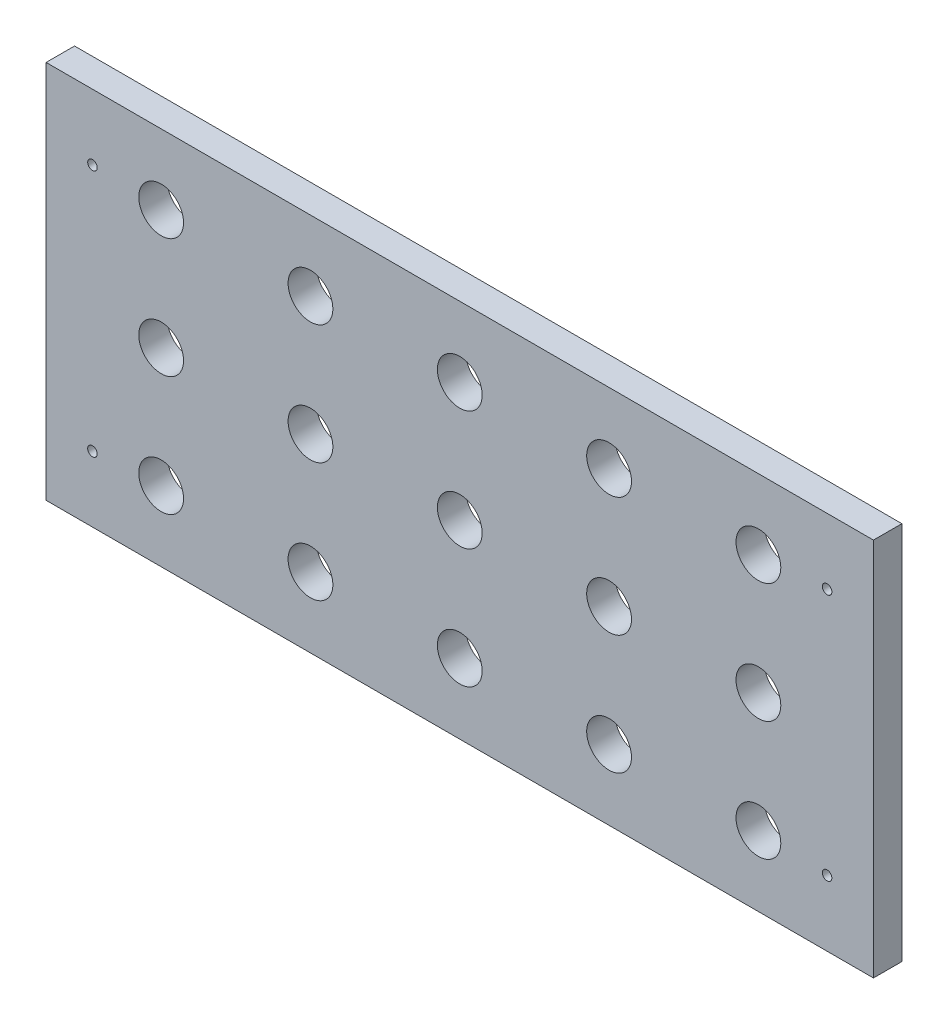
SolidWorks part; units mm, degrees
ref_plane "Front Plane" through (0, 0, 0) normal (0, 0, 1) x (1, 0, 0)
ref_plane "Top Plane" through (0, 0, 0) normal (0, 1, 0) x (1, 0, 0)
ref_plane "Right Plane" through (0, 0, 0) normal (1, 0, 0) x (0, 0, -1)
sketch "Sketch1" plane through (0, 0, 0) normal (0, 0, 1) x (1, 0, 0)
  line L1 (0, 0) -> (277.05, 0)
  line L2 (0, 0) -> (0, 127)
  line L3 (0, 127) -> (277.05, 127)
  line L4 (277.05, 0) -> (277.05, 127)
  line L5 (9.525, 127) -> (9.525, 0) construction
  line L7 (267.525, 127) -> (267.525, 0) construction
  circle A3 centre (15.525, 105) radius 1.6
  circle A4 centre (15.525, 22) radius 1.6
  circle A5 centre (261.525, 105) radius 1.6
  circle A6 centre (261.525, 22) radius 1.6
  dimension "D14" = 3.2
  dimension "D17" = 3.2
  dimension "D19" = 3.2
  dimension "D20" = 3.2
  dimension "D1" = 127
  dimension "D2" = 277.05
  dimension "D3" = 9.525
  dimension "D5" = 9.525
  dimension "D13" = 6
  dimension "D15" = 22
  dimension "D16" = 6
  dimension "D18" = 22
  dimension "D21" = 6
  dimension "D22" = 6
  dimension "D23" = 22
  dimension "D24" = 22
extrude "Wall" add sketch "Sketch1" along normal blind 9.525
sketch "Sketch2" plane through (0, 0, 9.525) normal (0, 0, 1) x (1, 0, 0)
  line L0 (277.05, 127) -> (0, 127) construction
  line L1 (0, 127) -> (0, 0) construction
  line L2 (95.53, 107.95) -> (138.525, 107.95) construction
  line L3 (181.52, 107.95) -> (138.525, 107.95) construction
  circle A0 centre (138.525, 107.95) radius 3.97
  circle A1 centre (95.53, 107.95) radius 3.97
  circle A2 centre (181.52, 107.95) radius 3.97
  point P4 (138.525, 127)
  dimension "D1" = 7.94
  dimension "D2" = 19.05
  dimension "D3" = 95.53
extrude "RodCutouts" [suppressed] cut sketch "Sketch2" against normal up to next
sketch "Sketch3" plane through (0, 0, 9.525) normal (0, 0, 1) x (1, 0, 0)
  line L0 (277.05, 127) -> (0, 127) construction
  line L1 (50.8, 89.7557) -> (226.25, 89.7557)
  line L2 (50.8, 89.7557) -> (50.8, 113.4443)
  line L3 (50.8, 113.4443) -> (226.25, 113.4443)
  line L4 (226.25, 89.7557) -> (226.25, 113.4443)
  line L5 (50.8, 89.7557) -> (226.25, 113.4443) construction
  line L6 (50.8, 113.4443) -> (226.25, 89.7557) construction
  line L7 (0, 127) -> (0, 0) construction
  point P0 (138.525, 101.6)
  point P9 (138.525, 127)
  dimension "D1" = 25.4
  dimension "D2" = 50.8
extrude "CannulusLargeCutout" [suppressed] cut sketch "Sketch3" against normal up to next
sketch "Sketch4" plane through (0, 0, 9.525) normal (0, 0, 1) x (1, 0, 0)
  line L0 (15.525, 103.5) -> (261.525, 103.5) construction
  line L1 (15.525, 105) -> (15.525, 22) construction
  line L2 (261.525, 105) -> (261.525, 22) construction
  circle A0 centre (38.525, 103.5) radius 7.5
  circle A1 centre (38.525, 63.5) radius 7.5
  circle A2 centre (88.525, 63.5) radius 7.5
  circle A3 centre (138.525, 63.5) radius 7.5
  circle A4 centre (88.525, 103.5) radius 7.5
  circle A5 centre (138.525, 103.5) radius 7.5
  circle A6 centre (188.525, 103.5) radius 7.5
  circle A7 centre (238.525, 103.5) radius 7.5
  circle A8 centre (188.525, 63.5) radius 7.5
  circle A9 centre (238.525, 63.5) radius 7.5
  circle A10 centre (38.525, 23.5) radius 7.5
  circle A11 centre (88.525, 23.5) radius 7.5
  circle A12 centre (138.525, 23.5) radius 7.5
  circle A13 centre (188.525, 23.5) radius 7.5
  circle A14 centre (238.525, 23.5) radius 7.5
  point P9 (15.525, 63.5)
  point P23 (138.525, 103.5)
  dimension "D1" = 15
  dimension "D2" = 5
  dimension "D4" = 3
extrude "CannulusHoles" cut sketch "Sketch4" against normal up to next
equation "\"Length\"= 283mm"
equation "\"Width\"= 225mm"
equation "\"WallThickness\"= 12.5mm"
equation "\"UpperWaterJacketThickness\"= 28mm"
equation "\"SpacerHeight\"= 80.2mm"
equation "\"SpacerCornerWidth\"= 10mm"
equation "\"SpacerCornerHeight\"= 60.16mm"
equation "\"SpacerPegDiameter\"= 10mm"
equation "\"SpacerPegHeight\"= 10mm"
equation "\"TubingShort\"= 110mm"
equation "\"TubingLong\"= 175mm"
equation "\"PlateLength\"= 252mm"
equation "\"PlateWidth\"= 190mm"
equation "\"PlateHoleDiameter\"= 5.9mm"
equation "\"PlateHoleBottom\"= 2mm"
equation "\"PlateHoleSide\"= 1.55mm"
equation "\"PlateHoleSpacing\"= 3.1mm"
equation "\"PlateThickness\"= 1.55mm"
equation "\"ReservoirBottom\"= 12.5mm"
equation "\"ReservoirSupportWidth\"= 12mm"
equation "\"ReservoirSupportHeight\"= 15.1mm"
equation "\"ReservoirSupportPlacementHeight\"= 50mm"
equation "\"ReservoirHoleDiameter\"= 12.7mm"
equation "\"ReservoirHoleRight\"= 25mm"
equation "\"ReservoirHoleTop\"= \"ReservoirSupportPlacementHeight\""
equation "\"ReservoirHeight\"= 90mm"
equation "\"ReservoirPortBottom\"= 4mm"
equation "\"ReservoirPortTop\"= 10mm"
equation "\"ReservoirPortWidth\"= 101mm"
equation "\"CustomSpacerWallThickness\"= 0.375in"
equation "\"CustomSpacerHeight\"= 5in"
equation "\"CustomSpacerRodHoleHeight\"= .75in"
equation "\"CustomSpacerRodHoleDiameter\"= .3125in"
equation "\"ScrewBlockSide\"= 12mm"
equation "\"ScrewBlockUpperHeight\"= 16mm"
equation "\"ScrewBlockLowerHeight\"= 16mm"
equation "\"InternalLength\"= \"Length\" - ( 2 * \"WallThickness\" )"
equation "\"InternalWidth\"= \"Width\" - ( 2 * \"WallThickness\" )"
equation "\"CustomSpacerPegHeight\"= 1in"
equation "\"CustomSpacerScrewBore\"=3.2mm"
equation "\"CustomSpacerScrewDepth\"=10mm"
equation "\"D1@Sketch1\"=\"CustomSpacerHeight\""
equation "\"D2@Sketch1\"=\"InternalLength\"+\"CustomSpacerWallThickness\"*2"
equation "\"D3@Sketch1\"=\"CustomSpacerWallThickness\""
equation "\"D5@Sketch1\"=\"CustomSpacerWallThickness\""
equation "\"D1@Wall\" = \"CustomSpacerWallThickness\""
equation "\"D13@Sketch1\"=\"ScrewBlockSide\"/2"
equation "\"D14@Sketch1\"=\"CustomSpacerScrewBore\""
equation "\"D15@Sketch1\"=\"ScrewBlockUpperHeight\"+\"ScrewBlockSide\"/2"
equation "\"D16@Sketch1\"=\"ScrewBlockSide\"/2"
equation "\"D17@Sketch1\"=\"CustomSpacerScrewBore\""
equation "\"D18@Sketch1\"=\"ScrewBlockLowerHeight\"+\"ScrewBlockSide\"/2"
equation "\"D19@Sketch1\"=\"CustomSpacerScrewBore\""
equation "\"D20@Sketch1\"=\"CustomSpacerScrewBore\""
equation "\"D21@Sketch1\"=\"ScrewBlockSide\"/2"
equation "\"D22@Sketch1\"=\"ScrewBlockSide\"/2"
equation "\"D23@Sketch1\"=\"ScrewBlockLowerHeight\"+\"ScrewBlockSide\"/2"
equation "\"D24@Sketch1\"=\"ScrewBlockUpperHeight\"+\"ScrewBlockSide\"/2"
equation "\"RodCutout\"=7.94"
equation "\"D1@Sketch2\"=\"RodCutout\""
equation "\"D3@Sketch2\"=86mm+9.53mm"
equation "\"CannulusTubingDiameter\"=15"
equation "\"D1@Sketch4\"=\"CannulusTubingDiameter\""
